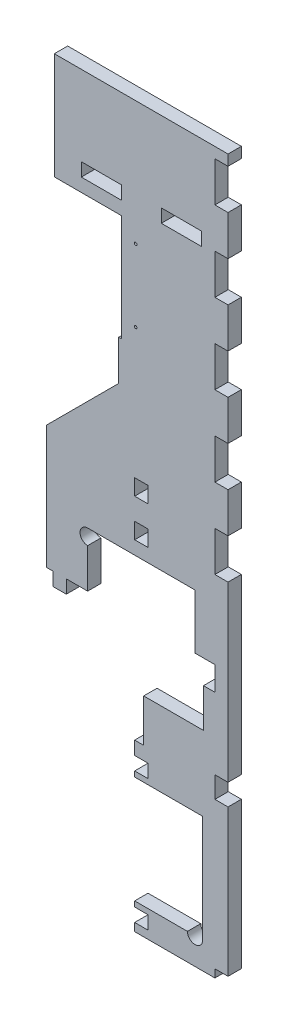
SolidWorks part; units mm, degrees
material "Balsa"
ref_plane "Plan de face" through (0, 0, 0) normal (0, 0, 1) x (1, 0, 0)
ref_plane "Plan de dessus" through (0, 0, 0) normal (0, 1, 0) x (1, 0, 0)
ref_plane "Plan de droite" through (0, 0, 0) normal (1, 0, 0) x (0, 0, -1)
sketch "Esquisse1" plane through (0, 0, 0) normal (0, 0, 1) x (1, 0, 0)
  line L0 (65.1211, 0) -> (30.1224, 0)
  line L2 (65.1211, 0) -> (65.1211, 270)
  line L3 (65.1211, 270) -> (0, 270)
  line L4 (0, 270) -> (0, 230)
  line L5 (0, 230) -> (24.1211, 230)
  line L6 (-2.8789, 101.7504) -> (12.493, 101.7504)
  line L7 (12.493, 101.7504) -> (12.493, 122.247)
  line L8 (12.493, 122.247) -> (52.693, 122.247)
  line L9 (52.693, 122.247) -> (52.693, 101.7504)
  line L10 (52.693, 101.7504) -> (55.9116, 101.7504)
  line L11 (1.3186, 101.7504) -> (30.1224, 101.7504) construction
  line L12 (55.9116, 101.7504) -> (55.9116, 78.2407)
  line L13 (55.9116, 78.2407) -> (33.5123, 78.2407)
  line L14 (33.5123, 78.2407) -> (33.5123, 62.2)
  line L15 (33.5123, 62.2) -> (30.1224, 62.2)
  line L16 (30.1224, 62.2) -> (30.1224, 57.2)
  line L17 (30.1224, 50.2) -> (55.6176, 50.2)
  line L18 (30.1224, 57.2) -> (35.1224, 57.2)
  line L19 (24.1211, 230) -> (24.1211, 175)
  line L20 (35.1224, 57.2) -> (35.1224, 52.2)
  line L21 (24.1211, 175) -> (-2.8789, 148)
  line L22 (-2.8789, 148) -> (-2.8789, 101.7504)
  line L23 (35.1224, 52.2) -> (30.1224, 52.2)
  line L24 (30.1224, 52.2) -> (30.1224, 50.2)
  line L25 (30.1224, 0) -> (30.1224, 3)
  line L26 (30.1224, 3) -> (35.1224, 3)
  line L27 (35.1224, 3) -> (35.1224, 8)
  line L30 (35.1224, 8) -> (30.1224, 8)
  line L31 (30.1224, 8) -> (30.1224, 10)
  line L32 (30.1224, 10) -> (55.6176, 10)
  line L33 (55.6176, 10) -> (55.6176, 50.2)
  dimension "D1" = 270
  dimension "D2" = 65.1211
  dimension "D3" = 40.2
  dimension "D4" = 2
  dimension "D5" = 20.4965
  dimension "D6" = 40.2
  dimension "D7" = 55
  dimension "D8" = 40
  dimension "D9" = 12.4281
  dimension "D10" = 25.4952
  dimension "D11" = 5
  dimension "D12" = 5
  dimension "D13" = 5
  dimension "D14" = 2
  dimension "D15" = 5
  dimension "D16" = 5
  dimension "D17" = 25.4952
  dimension "D18" = 135
  dimension "D19" = 41
  dimension "D20" = 68
extrude "Boss.-Extru.1" add sketch "Esquisse1" against normal blind 5
sketch "Esquisse2" plane through (0, 0, 0) normal (0, 0, 1) x (1, 0, 0)
  line L0 (52.693, 101.7504) -> (55.9116, 101.7504) construction
  line L1 (35.1224, 147.4016) -> (30.1224, 147.4016)
  line L2 (12.493, 122.247) -> (52.693, 122.247) construction
  line L3 (12.493, 101.7504) -> (12.493, 122.247) construction
  line L4 (35.1224, 147.4016) -> (35.1224, 141.4016)
  line L5 (35.1224, 141.4016) -> (30.1224, 141.4016)
  line L6 (30.1224, 147.4016) -> (30.1224, 141.4016)
  line L7 (35.1224, 133.247) -> (30.1224, 133.247)
  line L8 (35.1224, 133.247) -> (35.1224, 127.247)
  line L9 (35.1224, 127.247) -> (30.1224, 127.247)
  line L10 (30.1224, 133.247) -> (30.1224, 127.247)
  line L11 (55.9116, 101.7504) -> (60.186, 101.7504)
  line L12 (55.9116, 101.7504) -> (55.9116, 92.7704)
  line L13 (55.9116, 92.7704) -> (60.186, 92.7704)
  line L14 (60.186, 101.7504) -> (60.186, 92.7704)
  line L15 (52.693, 122.247) -> (52.693, 101.7504) construction
  line L16 (65.1211, 0) -> (65.1211, 270) construction
  line L17 (65.1211, 0) -> (60.2011, 0)
  line L18 (65.1211, 0) -> (65.1211, 3)
  line L19 (65.1211, 3) -> (60.2011, 3)
  line L20 (60.2011, 0) -> (60.2011, 3)
  line L21 (30.1224, 0) -> (65.1211, 0) construction
  line L22 (65.1211, 0) -> (65.1211, 270) construction
  line L23 (65.1211, 58) -> (60.2011, 58)
  line L24 (65.1211, 58) -> (65.1211, 66)
  line L25 (65.1211, 66) -> (60.2011, 66)
  line L26 (60.2011, 58) -> (60.2011, 66)
  line L27 (30.1224, 0) -> (65.1211, 0) construction
  line L28 (65.1211, 161) -> (60.2011, 161)
  line L29 (65.1211, 131) -> (60.2011, 131)
  line L30 (65.1211, 131) -> (65.1211, 146)
  line L31 (65.1211, 146) -> (60.2011, 146)
  line L32 (60.2011, 131) -> (60.2011, 146)
  line L33 (65.1211, 161) -> (65.1211, 176)
  line L34 (65.1211, 176) -> (60.2011, 176)
  line L35 (60.2011, 161) -> (60.2011, 176)
  line L36 (65.1211, 191) -> (60.2011, 191)
  line L37 (65.1211, 191) -> (65.1211, 206)
  line L38 (65.1211, 206) -> (60.2011, 206)
  line L39 (60.2011, 191) -> (60.2011, 206)
  line L40 (65.1211, 221) -> (60.2011, 221)
  line L41 (65.1211, 221) -> (65.1211, 236)
  line L42 (65.1211, 236) -> (60.2011, 236)
  line L43 (60.2011, 221) -> (60.2011, 236)
  line L44 (65.1211, 251) -> (60.2011, 251)
  line L45 (65.1211, 251) -> (65.1211, 266)
  line L46 (65.1211, 266) -> (60.2011, 266)
  line L47 (60.2011, 251) -> (60.2011, 266)
  line L48 (55.6176, 10) -> (30.1224, 10) construction
  line L49 (55.1211, 235) -> (40.1211, 235)
  line L50 (55.1211, 235) -> (55.1211, 240)
  line L51 (55.1211, 240) -> (40.1211, 240)
  line L52 (40.1211, 235) -> (40.1211, 240)
  line L53 (24.1211, 230) -> (24.1211, 175) construction
  line L54 (25.1211, 235) -> (10.1211, 235)
  line L55 (25.1211, 235) -> (25.1211, 240)
  line L56 (25.1211, 240) -> (10.1211, 240)
  line L57 (10.1211, 235) -> (10.1211, 240)
  line L58 (24.1211, 230) -> (25.1211, 230)
  line L59 (24.1211, 230) -> (24.1211, 190)
  line L60 (24.1211, 190) -> (25.1211, 190)
  line L61 (25.1211, 230) -> (25.1211, 190)
  line L62 (0, 230) -> (24.1211, 230) construction
  line L63 (65.1211, 270) -> (0, 270) construction
  line L64 (55.6176, 50.2) -> (55.6176, 10) construction
  circle A0 centre (12.493, 119.3895) radius 2.8575
  circle A1 centre (30.493, 223.5) radius 0.5
  circle A2 centre (30.493, 196.5) radius 0.5
  circle A3 centre (52.7601, 10) radius 2.8575
  dimension "D15" = 5.715
  dimension "D1" = 2.8575
  dimension "D2" = 7.493
  dimension "D3" = 4.92
  dimension "D4" = 3
  dimension "D5" = 4.92
  dimension "D6" = 8
  dimension "D7" = 58
  dimension "D8" = 15
  dimension "D9" = 131
  dimension "D11" = 40
  dimension "D12" = 1
  dimension "D13" = 5
  dimension "D14" = 30
  dimension "D10" = 5
extrude "Enlèv. mat.-Extru.1" cut sketch "Esquisse2" against normal blind 5
sketch "Esquisse3" plane through (0, 0, 0) normal (0, 0, 1) x (1, 0, 0)
  line L1 (4.493, 101.7504) -> (-0.507, 101.7504)
  line L2 (4.493, 101.7504) -> (4.493, 96.7504)
  line L3 (4.493, 96.7504) -> (-0.507, 96.7504)
  line L4 (-0.507, 101.7504) -> (-0.507, 96.7504)
  line L6 (-2.8789, 101.7504) -> (12.493, 101.7504) construction
  line L7 (12.493, 101.7504) -> (12.493, 116.532) construction
  dimension "D1" = 8
  dimension "D2" = 5
  dimension "D3" = 5
extrude "Boss.-Extru.2" add sketch "Esquisse3" against normal blind 5
